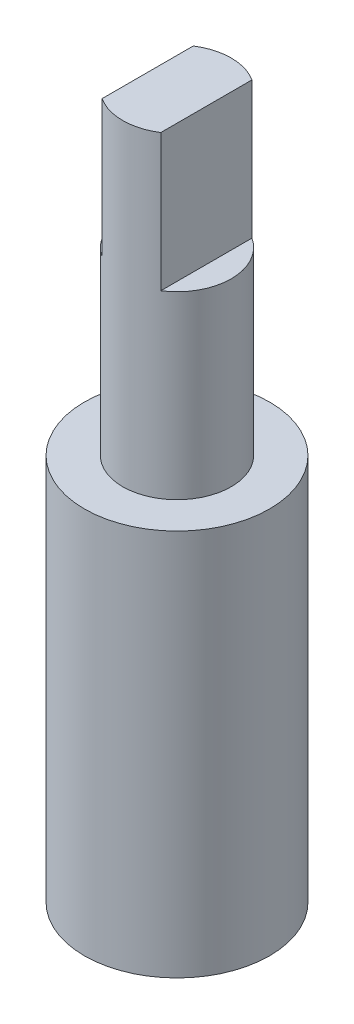
SolidWorks part; units mm, degrees
ref_plane "Front Plane" through (0, 0, 0) normal (0, 0, 1) x (1, 0, 0)
ref_plane "Top Plane" through (0, 0, 0) normal (0, 1, 0) x (1, 0, 0)
ref_plane "Right Plane" through (0, 0, 0) normal (1, 0, 0) x (0, 0, -1)
sketch "Sketch1" plane through (0, 0, 0) normal (0, 1, 0) x (1, 0, 0)
  circle A0 centre (0, 0) radius 3.075
  dimension "D1" = 6.15
extrude "Boss-Extrude1" add sketch "Sketch1" along normal blind 12.85
sketch "Sketch2" plane through (0, 12.85, 0) normal (0, 1, 0) x (1, 0, 0)
  circle A0 centre (0, 0) radius 1.8
  dimension "D1" = 3.6
extrude "Boss-Extrude2" add sketch "Sketch2" along normal blind 5.98
sketch "Sketch3" plane through (0, 18.83, 0) normal (0, 1, 0) x (1, 0, 0)
  line L0 (-0.975, 1.5131) -> (-0.975, -1.5131)
  line L1 (0.975, 1.5131) -> (0.975, -1.5131)
  circle A0 centre (0, 0) radius 1.8 construction
  circle A1 centre (0, 0) radius 1.8 construction
  arc A2 (-0.975, -1.5131) -> (0.975, -1.5131) centre (0, 0) ccw
  arc A3 (0.975, 1.5131) -> (-0.975, 1.5131) centre (0, 0) ccw
  point P4 (-1.8, 0)
  point P5 (1.8, 0)
  dimension "D1" = 1.95
  dimension "D2" = 0.975
extrude "Boss-Extrude3" add sketch "Sketch3" along normal blind 4.55
sketch "Sketch4" plane through (0, 0, 0) normal (0, -1, 0) x (1, 0, 0)
  circle A0 centre (0, 0) radius 2.15
  dimension "D1" = 4.3
extrude "Cut-Extrude1" cut sketch "Sketch4" against normal blind 1.95
